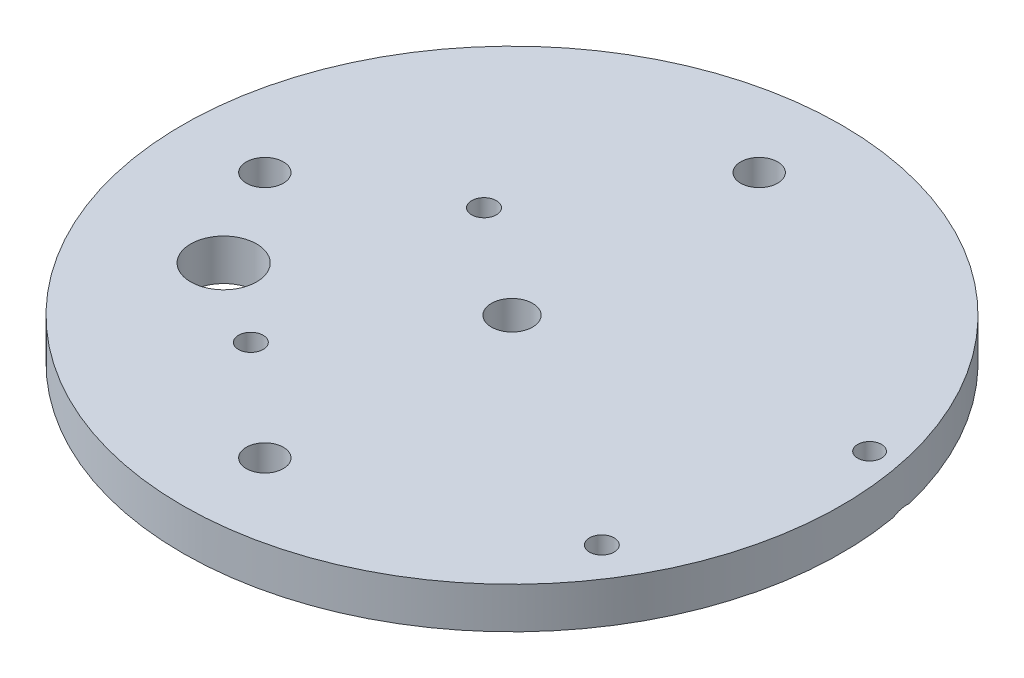
SolidWorks part; units mm, degrees
ref_plane "Front Plane" through (0, 0, 0) normal (0, 0, 1) x (1, 0, 0)
ref_plane "Top Plane" through (0, 0, 0) normal (0, 1, 0) x (1, 0, 0)
ref_plane "Right Plane" through (0, 0, 0) normal (1, 0, 0) x (0, 0, -1)
sketch "Sketch1" plane through (0, 0, 0) normal (0, 1, 0) x (1, 0, 0)
  circle A0 centre (0, 0) radius 40
  circle A1 centre (0, 0) radius 2.5
extrude "Boss-Extrude1" add sketch "Sketch1" along normal blind 5
sketch "Sketch2" plane through (0, 0, 0) normal (0, -1, 0) x (1, 0, 0)
  circle A0 centre (0, 0) radius 8
  circle A1 centre (0, 0) radius 2.5
extrude "Boss-Extrude2" add sketch "Sketch2" along normal blind 10
hole_wizard "M4x0.7 Tapped Hole1" positions "3DSketch1" profile "Sketch3" tap size "M4x0.7" standard "ANSI Metric"
sketch3d "3DSketch1"
  point P0 (8, -5, 0)
sketch "Sketch3" plane through (8, -5, 0) normal (0, 1, 0) x (0, 0, -1)
  line L0 (0, 0) -> (0, 10.0914)
  line L1 (0, 10.0914) -> (1.65, 9.1)
  line L2 (1.65, 9.1) -> (1.65, 0)
  line L5 (1.65, 0) -> (0, 0)
  line L10 (0, 10.0914) -> (-1.65, 9.1) construction
  line L11 (0, -6.35) -> (0, 107.95) construction
  dimension "Tap Drill Dia." = 3.3
  dimension "Tap Drill Depth" = 9.1
  dimension "Drill Angle" = 118
sketch "Sketch4" plane through (0, 5, 0) normal (0, 1, 0) x (1, 0, 0)
  circle A0 centre (0, 30) radius 2.25
  circle A1 centre (0, -30) radius 2.25
  circle A2 centre (-30, 0) radius 2.25
extrude "Cut-Extrude1" cut sketch "Sketch4" against normal blind 15
sketch "Sketch5" plane through (0, 5, 0) normal (0, 1, 0) x (1, 0, 0)
  circle A0 centre (-13, 9.6) radius 1.5
  circle A1 centre (36, 7.4) radius 1.4513
  circle A2 centre (29.6, -18.7) radius 1.5
  circle A3 centre (-13, -18.7) radius 1.5
extrude "Cut-Extrude2" cut sketch "Sketch5" against normal blind 15
sketch "Sketch6" plane through (0, 5, 0) normal (0, 1, 0) x (1, 0, 0)
  circle A0 centre (-23, -12) radius 4
extrude "Cut-Extrude3" cut sketch "Sketch6" against normal blind 15
chamfer "Chamfer2" distance 2 angle 45 4 edges at (36, 0, -5.9487) (29.6, 0, 20.2) (-13, 0, 20.2) (-13, 0, -8.1)
